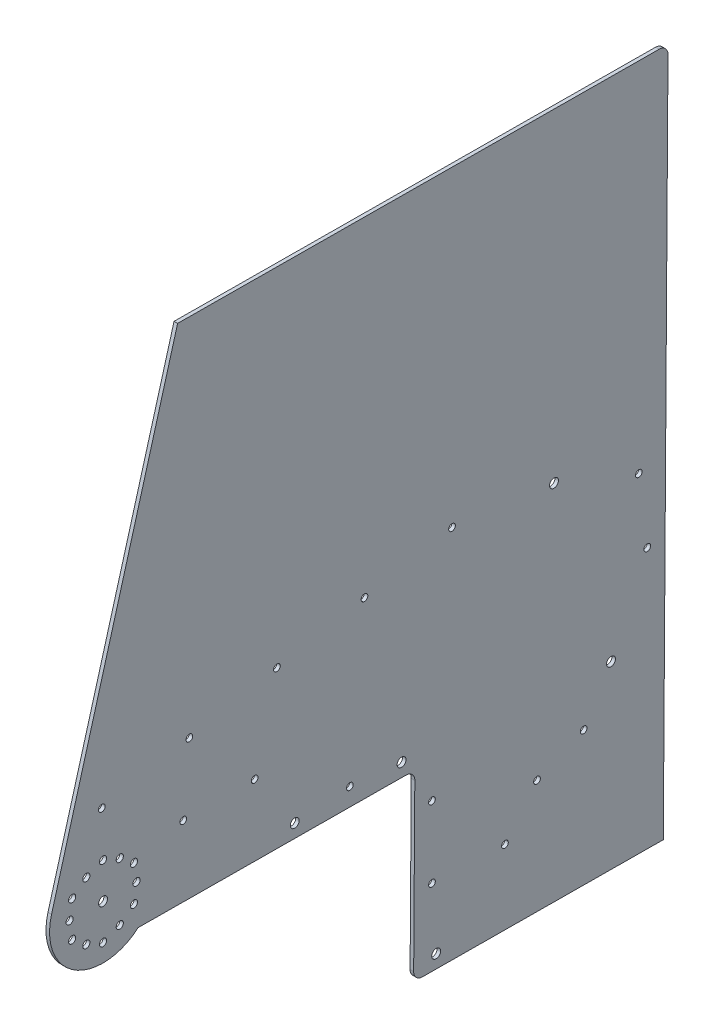
SolidWorks part; units mm, degrees
ref_plane "Front Plane" through (0, 0, 0) normal (0, 0, 1) x (1, 0, 0)
ref_plane "Top Plane" through (0, 0, 0) normal (0, 1, 0) x (1, 0, 0)
ref_plane "Right Plane" through (0, 0, 0) normal (1, 0, 0) x (0, 0, -1)
sketch "Sketch1" plane through (2097.3395, 0, 0) normal (1, 0, 0) x (0, 0, -1)
  line L0 (818.1062, 61.7756) -> (405.1402, 61.7756) construction
  line L6 (470.4626, 294.284) -> (380.6906, -25.2502)
  line L7 (442.3722, -64.3046) -> (633.0668, -65.629)
  line L8 (639.3726, -72.023) -> (638.5567, -189.4951)
  line L9 (644.8624, -195.8891) -> (816.3083, -197.0799)
  line L10 (816.3083, -197.0799) -> (819.6601, 285.5085)
  line L11 (813.3543, 291.9025) -> (470.4626, 294.284)
  line L12 (470.4626, 294.284) -> (380.6906, -25.2502)
  line L13 (442.3722, -64.3046) -> (633.0668, -65.629)
  line L14 (639.3726, -72.023) -> (638.5567, -189.4951)
  line L15 (644.8624, -195.8891) -> (816.3083, -197.0799)
  line L16 (816.3083, -197.0799) -> (819.6601, 285.5085)
  line L17 (813.3543, 291.9025) -> (470.4626, 294.284)
  circle A0 centre (553.8955, -55.5539) radius 9.525 construction
  circle A1 centre (629.9581, -56.0822) radius 9.525 construction
  circle A2 centre (654.5854, -186.4314) radius 9.525 construction
  circle A3 centre (779.0999, -68.5703) radius 25.4 construction
  arc A4 (380.6906, -25.2502) -> (442.3722, -64.3046) centre (417.3705, -35.5552) ccw
  arc A5 (639.3726, -72.023) -> (633.0668, -65.629) centre (633.0227, -71.9789) ccw
  arc A6 (638.5567, -189.4951) -> (644.8624, -195.8891) centre (644.9065, -189.5392) ccw
  arc A7 (819.6601, 285.5085) -> (813.3543, 291.9025) centre (813.3102, 285.5526) ccw
  arc A8 (380.6906, -25.2502) -> (442.3722, -64.3046) centre (417.3705, -35.5552) ccw
  arc A9 (639.3726, -72.023) -> (633.0668, -65.629) centre (633.0227, -71.9789) ccw
  arc A10 (638.5567, -189.4951) -> (644.8624, -195.8891) centre (644.9065, -189.5392) ccw
  arc A11 (819.6601, 285.5085) -> (813.3543, 291.9025) centre (813.3102, 285.5526) ccw
  circle A12 centre (553.8955, -55.5539) radius 3.175
  circle A13 centre (553.8955, -55.5539) radius 9.525 construction
  circle A14 centre (629.9581, -56.0822) radius 9.525 construction
  circle A15 centre (654.5854, -186.4314) radius 9.525 construction
  circle A16 centre (779.0999, -68.5703) radius 25.4 construction
  circle A17 centre (738.492, 61.7756) radius 25.4 construction
  circle A18 centre (738.492, 61.7756) radius 3.175
  circle A19 centre (779.0999, -68.5703) radius 3.175
  circle A20 centre (654.5854, -186.4314) radius 3.175
  circle A23 centre (417.3705, -35.5552) radius 3.175
  circle A24 centre (629.9581, -56.0822) radius 3.175
  circle M11 centre (417.3705, -35.5552) radius 15.875
  line M12 (470.4626, 294.284) -> (380.6906, -25.2502)
  arc M13 (380.6906, -25.2502) -> (442.3722, -64.3046) centre (417.3705, -35.5552) ccw
  line M14 (442.3722, -64.3046) -> (633.0668, -65.629)
  arc M15 (633.0668, -65.629) -> (639.3726, -72.023) centre (633.0227, -71.9789) cw
  line M16 (639.3726, -72.023) -> (638.5567, -189.4951)
  arc M17 (638.5567, -189.4951) -> (644.8624, -195.8891) centre (644.9065, -189.5392) ccw
  line M18 (644.8624, -195.8891) -> (816.3083, -197.0799)
  line M19 (816.3083, -197.0799) -> (819.6601, 285.5085)
  arc M20 (819.6601, 285.5085) -> (813.3543, 291.9025) centre (813.3102, 285.5526) ccw
  line M21 (813.3543, 291.9025) -> (470.4626, 294.284)
  dimension "D2" = 6.35
  dimension "D5" = 6.35
  dimension "D3" = 232.5083
  dimension "D4" = 136.525
  dimension "D1" = 0
extrude "Boss-Extrude1" add sketch "Sketch1" along normal blind 2.54 contours A24 A20 A19 A18 M21 M12 M13 M14 M15 M16 M17 M18 M19 M20 M11 | A23 M11 region at (2097.3395, 73.9165, -634.5049) region at (2097.3395, -35.5552, -401.9445)
sketch "Sketch2" plane through (2099.8795, 0, 0) normal (1, 0, 0) x (0, 0, -1)
  circle A1 centre (759.6181, -100.9825) radius 2.3813
  circle A2 centre (759.6181, -100.9825) radius 2.3813
  circle A3 centre (541.1877, 46.532) radius 2.3813
  circle A4 centre (541.1877, 46.532) radius 2.3812
  circle A5 centre (478.8516, 34.4297) radius 2.3813
  circle A6 centre (478.8516, 34.4297) radius 2.3813
  circle A7 centre (416.5156, 22.3274) radius 2.3813
  circle A8 centre (416.5156, 22.3274) radius 2.3813
  circle A9 centre (525.3205, -14.245) radius 2.3813
  circle A10 centre (525.3205, -14.245) radius 2.3813
  circle A11 centre (798.8869, 37.4794) radius 2.3813
  circle A12 centre (798.8869, 37.4794) radius 2.3813
  circle A13 centre (665.8598, 70.7367) radius 2.3813
  circle A14 centre (665.8598, 70.7367) radius 2.3812
  circle A15 centre (603.5237, 58.6344) radius 2.3813
  circle A16 centre (603.5237, 58.6344) radius 2.3812
  circle A17 centre (703.5591, -143.5195) radius 2.3813
  circle A18 centre (703.5591, -143.5195) radius 2.3813
  circle A19 centre (726.3842, -115.3922) radius 2.3813
  circle A20 centre (726.3842, -115.3922) radius 2.3813
  circle A21 centre (804.8987, -11.2496) radius 2.3813
  circle A22 centre (804.8987, -11.2496) radius 2.3813
  circle A23 centre (474.5205, -14.245) radius 2.3813
  circle A24 centre (474.5205, -14.245) radius 2.3813
  circle A25 centre (651.59, -141.5513) radius 2.3813
  circle A26 centre (651.59, -141.5513) radius 2.3813
  circle A27 centre (651.59, -90.7513) radius 2.3813
  circle A28 centre (651.59, -90.7513) radius 2.3813
  circle A29 centre (593.1285, -52.6513) radius 2.3813
  circle A30 centre (593.1285, -52.6513) radius 2.3813
  dimension "D1" = 0
  dimension "D2" = 0
  dimension "D3" = 0
  dimension "D4" = 0
  dimension "D5" = 0
  dimension "D6" = 0
  dimension "D7" = 0
  dimension "D8" = 0
  dimension "D9" = 0
  dimension "D10" = 0
  dimension "D11" = 0
  dimension "D12" = 0
  dimension "D13" = 0
  dimension "D14" = 0
  dimension "D15" = 0
extrude "Cut-Extrude1" cut sketch "Sketch2" against normal through all
sketch "Sketch4" plane through (2099.8795, 0, 0) normal (1, 0, 0) x (0, 0, -1)
  line L0 (-4.7879, -2.7643) -> (0, -5.5286)
  line L1 (0, -5.5286) -> (4.7879, -2.7643)
  line L2 (4.7879, -2.7643) -> (4.7879, 2.7643)
  line L3 (4.7879, 2.7643) -> (0, 5.5286)
  line L4 (0, 5.5286) -> (-4.7879, 2.7643)
  line L5 (-4.7879, 2.7643) -> (-4.7879, -2.7643)
  circle A0 centre (-11.9062, 20.6222) radius 2.5527
  circle A1 centre (0, 25.4) radius 2.5527
  circle A2 centre (-23.8125, 0) radius 2.5527
  circle A3 centre (-21.997, 12.7) radius 2.5527
  circle A4 centre (-11.9062, -20.6222) radius 2.5527
  circle A5 centre (-21.997, -12.7) radius 2.5527
  circle A6 centre (11.9062, -20.6222) radius 2.5527
  circle A7 centre (0, -25.4) radius 2.5527
  circle A8 centre (23.8125, 0) radius 2.5527
  circle A9 centre (21.997, -12.7) radius 2.5527
  circle A10 centre (11.9062, 20.6222) radius 2.5527
  circle A11 centre (21.997, 12.7) radius 2.5527
  circle A12 centre (0, 0) radius 30.1625
sketch "Sketch5" plane through (2099.8795, 0, 0) normal (1, 0, 0) x (0, 0, -1)
  line L0 (395.3735, -22.8552) -> (405.4643, -14.933) construction
  line L1 (405.4643, -14.933) -> (417.3705, -10.1552) construction
  line L2 (417.3705, -10.1552) -> (429.2768, -14.933) construction
  line L3 (429.2768, -14.933) -> (439.3675, -22.8552) construction
  line L4 (439.3675, -22.8552) -> (441.183, -35.5552) construction
  line L5 (441.183, -35.5552) -> (439.3675, -48.2552) construction
  line L6 (439.3675, -48.2552) -> (429.2768, -56.1775) construction
  line L7 (429.2768, -56.1775) -> (417.3705, -60.9552) construction
  line L8 (417.3705, -60.9552) -> (405.4643, -56.1775) construction
  line L9 (405.4643, -56.1775) -> (395.3735, -48.2552) construction
  line L10 (395.3735, -48.2552) -> (393.558, -35.5552) construction
  line L11 (393.558, -35.5552) -> (395.3735, -22.8552) construction
  circle A1 centre (417.3705, -35.5552) radius 3.175 construction
  circle A2 centre (395.3735, -48.2552) radius 2.5527
  circle A3 centre (417.3705, -35.5552) radius 3.175 construction
  circle A4 centre (405.4643, -56.1775) radius 2.5527
  circle A6 centre (395.3735, -22.8552) radius 2.5527
  circle A8 centre (393.558, -35.5552) radius 2.5527
  circle A10 centre (417.3705, -10.1552) radius 2.5527
  circle A12 centre (405.4643, -14.933) radius 2.5527
  circle A14 centre (439.3675, -22.8552) radius 2.5527
  circle A16 centre (429.2768, -14.933) radius 2.5527
  circle A18 centre (439.3675, -48.2552) radius 2.5527
  circle A20 centre (441.183, -35.5552) radius 2.5527
  circle A22 centre (417.3705, -60.9552) radius 2.5527
  circle A24 centre (429.2768, -56.1775) radius 2.5527
  point P6 (0, 0)
  point P9 (0, 0)
  point P12 (0, 0)
  point P15 (0, 0)
  point P18 (419.2459, -39.1336)
  point P21 (425.6052, -37.612)
  point P33 (417.914, -35.5552)
  point P36 (0, 0)
extrude "Cut-Extrude2" cut sketch "Sketch5" against normal through all
